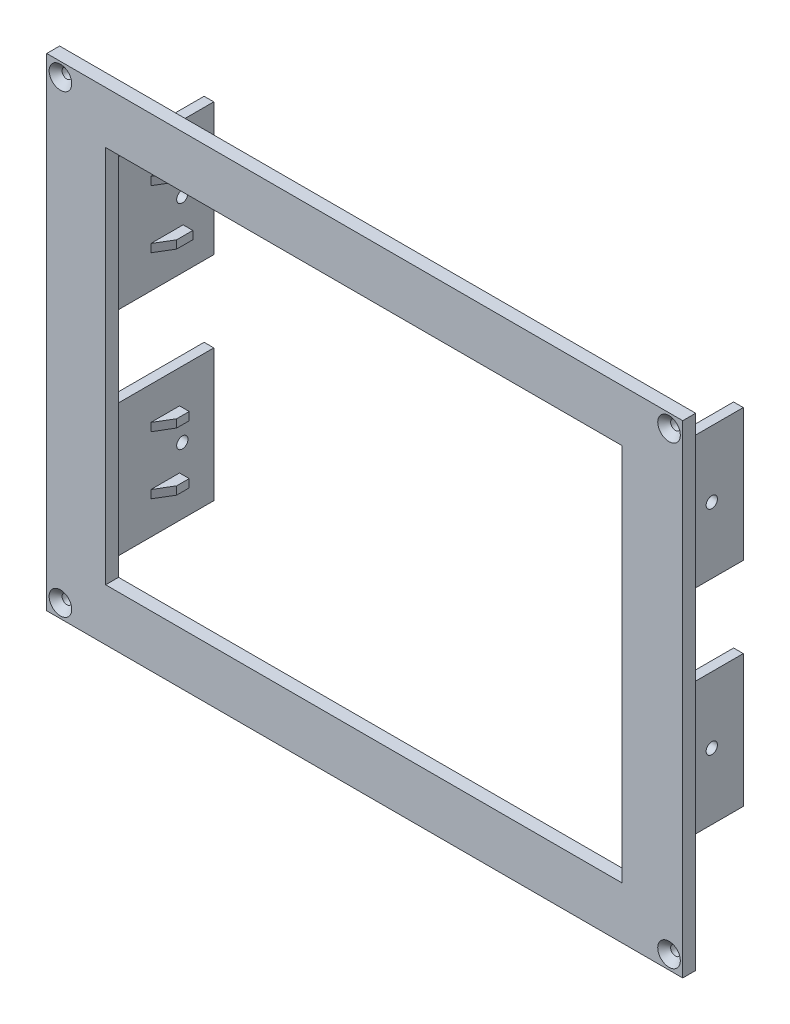
SolidWorks part; units mm, degrees
ref_plane "Plan de face" through (0, 0, 0) normal (0, 0, 1) x (1, 0, 0)
ref_plane "Plan de dessus" through (0, 0, 0) normal (0, 1, 0) x (1, 0, 0)
ref_plane "Plan de droite" through (0, 0, 0) normal (1, 0, 0) x (0, 0, -1)
sketch "Esquisse1" plane through (0, 0, 0) normal (0, 0, 1) x (1, 0, 0)
  line L1 (0, 0) -> (197, 0)
  line L2 (0, 0) -> (0, 149.5)
  line L3 (0, 149.5) -> (197, 149.5)
  line L4 (197, 0) -> (197, 149.5)
  dimension "D1" = 197
  dimension "D2" = 149.5
extrude "Boss.-Extru.1" add sketch "Esquisse1" along normal blind 4
sketch "Esquisse3" plane through (0, 0, 4) normal (0, 0, 1) x (1, 0, 0)
  line L0 (0, 149.5) -> (0, 0) construction
  line L1 (197, 149.5) -> (0, 149.5) construction
  line L2 (0, 0) -> (197, 0) construction
  line L3 (197, 0) -> (197, 149.5) construction
  circle A0 centre (4.25, 145.25) radius 1.5
  circle A2 centre (4.25, 4.25) radius 1.5
  circle A4 centre (192.75, 4.25) radius 1.5
  circle A6 centre (192.75, 145.25) radius 1.5
  dimension "D1" = 3
  dimension "D10" = 3
  dimension "D11" = 3
  dimension "D12" = 3
  dimension "D2" = 4.25
  dimension "D3" = 4.25
  dimension "D4" = 4.25
  dimension "D5" = 4.25
  dimension "D6" = 4.25
  dimension "D7" = 4.25
  dimension "D8" = 4.25
  dimension "D9" = 4.25
extrude "Enlèv. mat.-Extru.2" cut sketch "Esquisse3" against normal blind 4
chamfer "Chanfrein1" distance 2 angle 45 4 edges at (194.25, 145.25, 4) (194.25, 4.25, 4) (5.75, 4.25, 4) (5.75, 145.25, 4)
sketch "Esquisse4" plane through (0, 0, 4) normal (0, 0, 1) x (1, 0, 0)
  line L0 (197, 149.5) -> (0, 149.5) construction
  line L1 (18.25, 133.4) -> (178.25, 133.4)
  line L2 (18.25, 133.4) -> (18.25, 16.1)
  line L3 (18.25, 16.1) -> (178.25, 16.1)
  line L4 (178.25, 133.4) -> (178.25, 16.1)
  line L5 (0, 0) -> (197, 0) construction
  line L6 (0, 149.5) -> (0, 0) construction
  line L7 (197, 0) -> (197, 149.5) construction
  dimension "D1" = 117.3
  dimension "D2" = 160
  dimension "D3" = 16.1
  dimension "D4" = 16.1
  dimension "D5" = 18.25
  dimension "D6" = 18.75
extrude "Enlèv. mat.-Extru.3" cut sketch "Esquisse4" against normal blind 10
sketch "Esquisse5" plane through (0, 0, 0) normal (0, 0, -1) x (-1, 0, 0)
  line L2 (-178.75, 128.4) -> (-181.75, 128.4)
  line L3 (-178.75, 128.4) -> (-178.75, 87.4)
  line L4 (-178.75, 87.4) -> (-181.75, 87.4)
  line L5 (-181.75, 128.4) -> (-181.75, 87.4)
  line L6 (-18.25, 133.4) -> (-178.25, 133.4) construction
  line L7 (-178.25, 16.1) -> (-18.25, 16.1) construction
  line L8 (-178.75, 21.4) -> (-181.75, 21.4)
  line L9 (-178.75, 21.4) -> (-178.75, 62.4)
  line L10 (-178.75, 62.4) -> (-181.75, 62.4)
  line L11 (-181.75, 21.4) -> (-181.75, 62.4)
  line L12 (-178.25, 133.4) -> (-178.25, 16.1) construction
  line L13 (-18.25, 16.1) -> (-18.25, 133.4) construction
  line L14 (-17.75, 128.4) -> (-14.75, 128.4)
  line L15 (-17.75, 128.4) -> (-17.75, 87.4)
  line L16 (-17.75, 87.4) -> (-14.75, 87.4)
  line L17 (-14.75, 128.4) -> (-14.75, 87.4)
  line L18 (-17.75, 62.4) -> (-14.75, 62.4)
  line L19 (-17.75, 62.4) -> (-17.75, 21.4)
  line L20 (-17.75, 21.4) -> (-14.75, 21.4)
  line L21 (-14.75, 62.4) -> (-14.75, 21.4)
  dimension "D1" = 41
  dimension "D2" = 3
  dimension "D3" = 5
  dimension "D4" = 3
  dimension "D5" = 41
  dimension "D6" = 5.3
  dimension "D7" = 0.5
  dimension "D8" = 0.5
  dimension "D9" = 3
  dimension "D10" = 3
  dimension "D11" = 0.5
  dimension "D12" = 0.5
  dimension "D13" = 5.3
  dimension "D14" = 41
  dimension "D15" = 41
  dimension "D16" = 5
extrude "Boss.-Extru.2" add sketch "Esquisse5" along normal blind 30
sketch "Esquisse6" plane through (17.75, 0, 0) normal (1, 0, 0) x (0, 0, -1)
  line L0 (30, 128.4) -> (0, 128.4) construction
  line L1 (10.5, 118.15) -> (20.5, 118.15)
  line L2 (10.5, 118.15) -> (10.5, 115.65)
  line L3 (10.5, 115.65) -> (20.5, 115.65)
  line L4 (20.5, 118.15) -> (20.5, 115.65)
  line L5 (20.5, 100.15) -> (10.5, 100.15)
  line L6 (20.5, 100.15) -> (20.5, 97.65)
  line L7 (20.5, 97.65) -> (10.5, 97.65)
  line L8 (10.5, 100.15) -> (10.5, 97.65)
  line L9 (30, 87.4) -> (0, 87.4) construction
  line L10 (0, 128.4) -> (0, 87.4) construction
  line L11 (0, 62.4) -> (0, 21.4) construction
  line L12 (19.3828, 52.15) -> (10.5, 52.15)
  line L13 (19.3828, 52.15) -> (19.3828, 49.65)
  line L14 (19.3828, 49.65) -> (10.5, 49.65)
  line L15 (10.5, 52.15) -> (10.5, 49.65)
  line L16 (19.3828, 34.15) -> (10.5, 34.15)
  line L17 (19.3828, 34.15) -> (19.3828, 31.65)
  line L18 (19.3828, 31.65) -> (10.5, 31.65)
  line L19 (10.5, 34.15) -> (10.5, 31.65)
  line L20 (30, 21.4) -> (0, 21.4) construction
  line L21 (30, 62.4) -> (0, 62.4) construction
  dimension "D1" = 10.25
  dimension "D2" = 10.25
  dimension "D3" = 2.5
  dimension "D4" = 2.5
  dimension "D5" = 10.5
  dimension "D6" = 10.5
  dimension "D7" = 10
  dimension "D8" = 10
  dimension "D9" = 2.5
  dimension "D10" = 2.5
  dimension "D11" = 10.5
  dimension "D12" = 10.5
  dimension "D13" = 10.25
  dimension "D14" = 10.25
extrude "Boss.-Extru.3" add sketch "Esquisse6" along normal blind 3
sketch "Esquisse7" plane through (178.75, 0, 0) normal (-1, 0, 0) x (0, 0, 1)
  line L0 (-30, 128.4) -> (0, 128.4) construction
  line L1 (-20.5, 31.65) -> (-10.5, 31.65)
  line L2 (-20.5, 31.65) -> (-20.5, 34.15)
  line L3 (-20.5, 34.15) -> (-10.5, 34.15)
  line L4 (-10.5, 31.65) -> (-10.5, 34.15)
  line L5 (-20.5, 49.65) -> (-10.5, 49.65)
  line L6 (-20.5, 49.65) -> (-20.5, 52.15)
  line L7 (-20.5, 52.15) -> (-10.5, 52.15)
  line L8 (-10.5, 49.65) -> (-10.5, 52.15)
  line L9 (-20.5, 97.65) -> (-10.5, 97.65)
  line L10 (-20.5, 97.65) -> (-20.5, 100.15)
  line L11 (-20.5, 100.15) -> (-10.5, 100.15)
  line L12 (-10.5, 97.65) -> (-10.5, 100.15)
  line L13 (-20.5, 115.65) -> (-10.5, 115.65)
  line L14 (-20.5, 115.65) -> (-20.5, 118.15)
  line L15 (-20.5, 118.15) -> (-10.5, 118.15)
  line L16 (-10.5, 115.65) -> (-10.5, 118.15)
  line L17 (-30, 87.4) -> (0, 87.4) construction
  line L18 (-30, 62.4) -> (0, 62.4) construction
  line L19 (-30, 21.4) -> (0, 21.4) construction
  line L20 (0, 21.4) -> (0, 62.4) construction
  line L21 (0, 87.4) -> (0, 128.4) construction
  dimension "D1" = 2.5
  dimension "D2" = 2.5
  dimension "D3" = 2.5
  dimension "D4" = 2.5
  dimension "D5" = 10.25
  dimension "D6" = 10.25
  dimension "D7" = 10.25
  dimension "D8" = 10.25
  dimension "D9" = 10.5
  dimension "D10" = 10.5
  dimension "D11" = 10.5
  dimension "D12" = 10.5
  dimension "D13" = 10
  dimension "D14" = 10
  dimension "D15" = 10
  dimension "D16" = 10
extrude "Boss.-Extru.4" add sketch "Esquisse7" along normal blind 3
chamfer "Chanfrein2" distance 3 distance2 5 8 edges at (20.75, 98.9, -10.5) (20.75, 116.9, -10.5) (20.75, 32.9, -10.5) (20.75, 50.9, -10.5) (175.75, 116.9, -10.5) (175.75, 98.9, -10.5) (175.75, 50.9, -10.5) (175.75, 32.9, -10.5) first distance on face at (19.25, 98.9, -10.5) first distance on face at (19.25, 116.9, -10.5) first distance on face at (19.25, 32.9, -10.5) first distance on face at (19.25, 50.9, -10.5) first distance on face at (177.25, 116.9, -10.5) first distance on face at (177.25, 98.9, -10.5) first distance on face at (177.25, 50.9, -10.5) first distance on face at (177.25, 32.9, -10.5)
sketch "Esquisse8" plane through (14.75, 0, 0) normal (-1, 0, 0) x (0, 0, 1)
  line L0 (-30, 87.4) -> (0, 87.4) construction
  line L1 (-30, 128.4) -> (0, 128.4) construction
  line L2 (-30, 87.4) -> (-30, 128.4) construction
  line L3 (-30, 21.4) -> (0, 21.4) construction
  line L4 (-30, 21.4) -> (-30, 62.4) construction
  circle A0 centre (-20.25, 107.9) radius 1.75
  circle A1 centre (-20.25, 41.9) radius 1.75
  dimension "D1" = 3.5
  dimension "D5" = 3.5
  dimension "D2" = 20.5
  dimension "D3" = 20.5
  dimension "D4" = 9.75
  dimension "D6" = 20.5
  dimension "D7" = 9.75
extrude "Enlèv. mat.-Extru.4" cut sketch "Esquisse8" against normal blind 210
